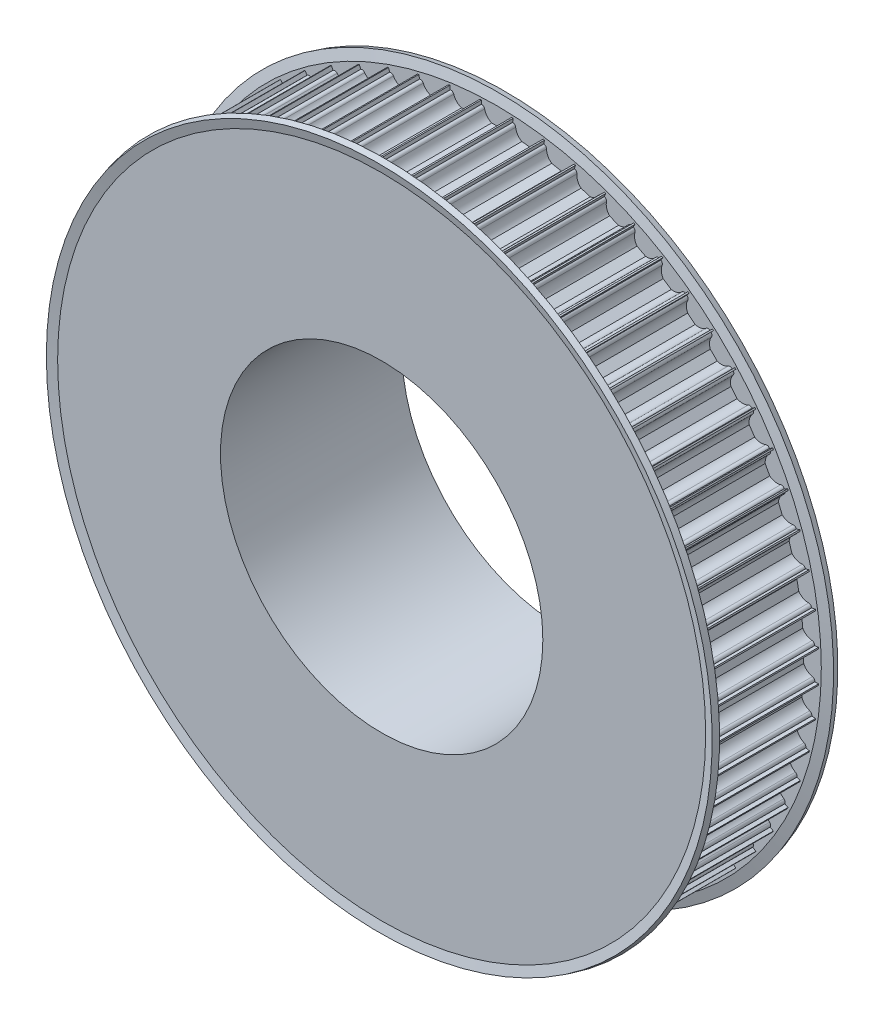
SolidWorks part; units mm, degrees
ref_plane "Front Plane" through (0, 0, 0) normal (0, 0, 1) x (1, 0, 0)
ref_plane "Top Plane" through (0, 0, 0) normal (0, 1, 0) x (1, 0, 0)
ref_plane "Right Plane" through (0, 0, 0) normal (1, 0, 0) x (0, 0, -1)
sketch "Sketch1" plane through (0, 0, 0) normal (1, 0, 0) x (0, 0, -1)
  line L0 (0, 0) -> (51.5673, 0) construction
  line L1 (-5, 40) -> (40, 40)
  line L2 (40, 40) -> (40, 55.5)
  line L3 (40, 55.5) -> (25, 55.5)
  line L4 (25, 55.5) -> (25, 80)
  line L5 (25, 80) -> (-5, 80)
  line L6 (-5, 80) -> (-5, 40)
  dimension "D1" = 80
  dimension "D2" = 40
  dimension "D3" = 30
  dimension "D4" = 15
  dimension "D5" = 15.5
revolve "Revolve1" add sketch "Sketch1" angle 360 about L0
sketch "Sketch2" plane through (0, 0, 5) normal (0, 0, 1) x (1, 0, 0)
  line L0 (-3.6742, 79) -> (-3.75, 79)
  line L1 (-3.75, 79) -> (-3.75, 81)
  line L2 (-3.75, 81) -> (3.75, 81)
  line L3 (3.75, 81) -> (3.75, 79)
  line L4 (3.75, 79) -> (3.6742, 79)
  line L5 (-1.199, 76.25) -> (1.199, 76.25)
  arc A0 (2.9394, 78.4) -> (1.199, 76.25) centre (0, 79) cw
  arc A1 (2.9394, 78.4) -> (3.6742, 79) centre (3.6742, 78.25) cw
  arc A2 (-2.9394, 78.4) -> (-3.6742, 79) centre (-3.6742, 78.25) ccw
  arc A3 (-1.199, 76.25) -> (-2.9394, 78.4) centre (0, 79) cw
  point P8 (0, 81)
  point P11 (3, 79)
  point P14 (-3, 79)
  dimension "D1" = 3
  dimension "D5" = 0.75
  dimension "D2" = 79
  dimension "D3" = 7.5
  dimension "D4" = 2
  dimension "D6" = 2.75
extrude "Cut-Extrude1" cut sketch "Sketch2" against normal up to next
pattern_circular "CirPattern1" count 64 over 360 about axis through (0, 0, 5) along (0, 0, 1) of "Cut-Extrude1"
sketch "Sketch3" plane through (0, 0, 0) normal (1, 0, 0) x (0, 0, -1)
  line L0 (10, -40.9775) -> (10, -16.0516) construction
  line L1 (25, -40.9775) -> (-5, -40.9775) construction
  line L2 (25, -16.0516) -> (-5, -16.0516) construction
  line L3 (25, 55.5) -> (25, 80.4125)
  line L4 (25, 80.4125) -> (25.592, 82.6218)
  line L5 (25.592, 82.6218) -> (24.1431, 83.01)
  line L6 (24.1431, 83.01) -> (23.5, 80.61)
  line L7 (23.5, 80.61) -> (23.5, 55.5)
  line L8 (23.5, 55.5) -> (25, 55.5)
  line L9 (-4.1431, 83.01) -> (-3.5, 80.61)
  line L10 (-3.5, 80.61) -> (-3.5, 55.5)
  line L11 (-3.5, 55.5) -> (-5, 55.5)
  line L12 (-5, 55.5) -> (-5, 80.4125)
  line L13 (-5, 80.4125) -> (-5.592, 82.6218)
  line L14 (-5.592, 82.6218) -> (-4.1431, 83.01)
  line L15 (0, 0) -> (-19.1733, 0) construction
  dimension "D1" = 15
  dimension "D2" = 1.5
  dimension "D3" = 25.11
  dimension "D4" = 2.4
revolve "Revolve2" add sketch "Sketch3" angle 360 about L15
